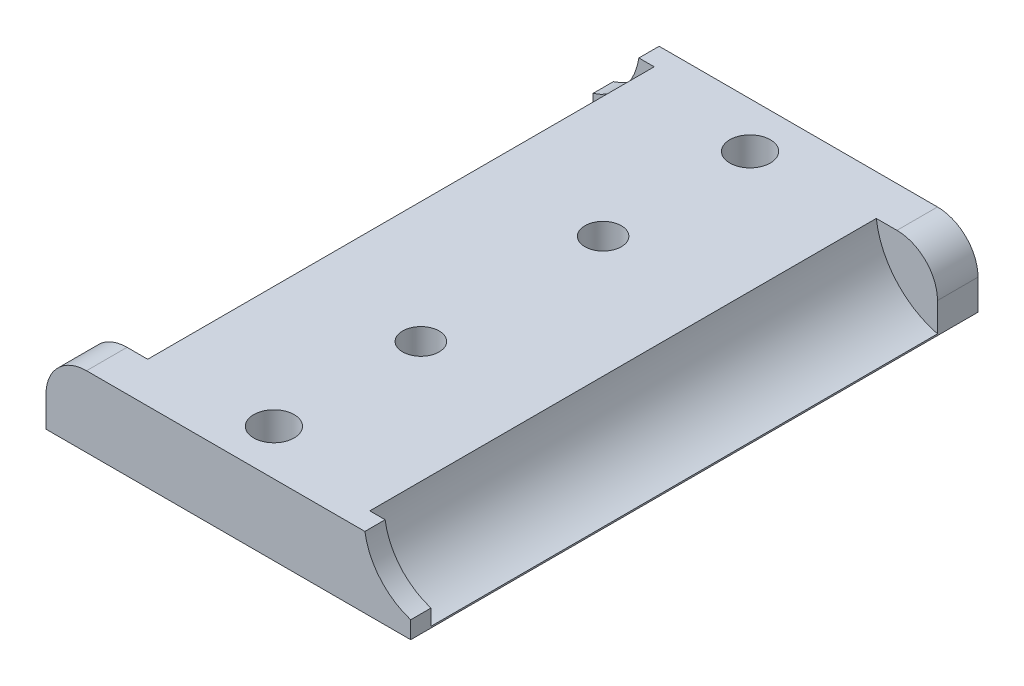
SolidWorks part; units mm, degrees
ref_plane "Front Plane" through (0, 0, 0) normal (0, 0, 1) x (1, 0, 0)
ref_plane "Top Plane" through (0, 0, 0) normal (0, 1, 0) x (1, 0, 0)
ref_plane "Right Plane" through (0, 0, 0) normal (1, 0, 0) x (0, 0, -1)
sketch "Sketch1" plane through (0, 0, 0) normal (0, 1, 0) x (1, 0, 0)
  line L1 (13.1473, -19.7747) -> (-4.8527, -19.7747)
  line L2 (13.1473, -19.7747) -> (13.1473, -47.7747)
  line L3 (13.1473, -47.7747) -> (-4.8527, -47.7747)
  line L4 (-4.8527, -19.7747) -> (-4.8527, -47.7747)
  dimension "D1" = 18
  dimension "D2" = 28
extrude "Boss-Extrude1" add sketch "Sketch1" along normal blind 4
sketch "Sketch2" plane through (0, 0, 19.7747) normal (0, 0, -1) x (-1, 0, 0)
  circle A0 centre (-14.1473, 4) radius 4.05
  circle A1 centre (5.8527, 4) radius 4.05
  dimension "D1" = 8.1
  dimension "D2" = 8.1
extrude "Cut-Extrude1" cut sketch "Sketch2" against normal through all
sketch "Sketch3" plane through (0, 4, 0) normal (0, 1, 0) x (1, 0, 0)
  circle A0 centre (4.1473, -38.2722) radius 0.9
  circle A1 centre (4.1473, -29.2771) radius 0.9
  dimension "D1" = 1.8
  dimension "D2" = 1.8
extrude "Cut-Extrude2" cut sketch "Sketch3" against normal blind 5
sketch "Sketch4" plane through (0, 0, 0) normal (0, -1, 0) x (1, 0, 0)
  circle A0 centre (4.1473, 29.2771) radius 1.6
  circle A1 centre (4.1473, 38.2722) radius 1.6
  dimension "D1" = 3.2
  dimension "D2" = 3.2
extrude "Cut-Extrude3" cut sketch "Sketch4" against normal blind 2
sketch "Sketch5" plane through (0, 4, 0) normal (0, 1, 0) x (1, 0, 0)
  line L0 (13.1473, -19.7747) -> (13.1473, -47.7747) construction
  line L1 (10.0973, -19.7747) -> (13.1473, -19.7747)
  line L2 (10.0973, -19.7747) -> (10.0973, -21.7747)
  line L3 (10.0973, -21.7747) -> (13.1473, -21.7747)
  line L4 (13.1473, -19.7747) -> (13.1473, -21.7747)
  line L5 (-4.8527, -47.7747) -> (-4.8527, -19.7747) construction
  line L6 (-1.8027, -47.7747) -> (-4.8527, -47.7747)
  line L7 (-1.8027, -47.7747) -> (-1.8027, -45.7747)
  line L8 (-1.8027, -45.7747) -> (-4.8527, -45.7747)
  line L9 (-4.8527, -47.7747) -> (-4.8527, -45.7747)
  dimension "D1" = 2
  dimension "D2" = 2
extrude "Boss-Extrude2" add sketch "Sketch5" against normal up to surface (4 mm away) up to face at (4.1473, 0, 27.6771)
sketch "Sketch6" plane through (0, 4, 0) normal (0, 1, 0) x (1, 0, 0)
  line L0 (13.1473, -21.7747) -> (13.1473, -47.7747) construction
  line L1 (10.0973, -47.7747) -> (13.1473, -47.7747)
  line L2 (10.0973, -47.7747) -> (10.0973, -46.7747)
  line L3 (10.0973, -46.7747) -> (13.1473, -46.7747)
  line L4 (13.1473, -47.7747) -> (13.1473, -46.7747)
  line L5 (-4.8527, -45.7747) -> (-4.8527, -19.7747) construction
  line L6 (-1.8027, -19.7747) -> (-4.8527, -19.7747)
  line L7 (-1.8027, -19.7747) -> (-1.8027, -20.7747)
  line L8 (-1.8027, -20.7747) -> (-4.8527, -20.7747)
  line L9 (-4.8527, -19.7747) -> (-4.8527, -20.7747)
  dimension "D1" = 1
  dimension "D2" = 1
extrude "Boss-Extrude3" add sketch "Sketch6" against normal up to surface (4 mm away) up to face at (4.1473, 0, 33.7747)
sketch "Sketch7" plane through (0, 0, 47.7747) normal (0, 0, 1) x (1, 0, 0)
  circle A0 centre (14.1473, 4) radius 3.3
  dimension "D1" = 6.6
extrude "Cut-Extrude4" cut sketch "Sketch7" against normal blind 2
sketch "Sketch8" plane through (0, 0, 19.7747) normal (0, 0, -1) x (-1, 0, 0)
  circle A0 centre (5.8527, 4) radius 3.3
  dimension "D1" = 6.6
extrude "Cut-Extrude5" cut sketch "Sketch8" against normal blind 2
sketch "Sketch9" plane through (0, 4, 0) normal (0, 1, 0) x (1, 0, 0)
  circle A0 centre (4.1473, -45.5247) radius 1
  circle A1 centre (4.1473, -22.0247) radius 1
  dimension "D1" = 2
  dimension "D2" = 2
extrude "Cut-Extrude6" cut sketch "Sketch9" against normal through all
sketch "Sketch10" plane through (0, 0, 0) normal (0, -1, 0) x (1, 0, 0)
  circle A0 centre (4.1473, 45.5247) radius 1.6
  circle A1 centre (4.1473, 22.0247) radius 1.6
  dimension "D1" = 3.2
  dimension "D2" = 3.2
extrude "Cut-Extrude7" cut sketch "Sketch10" against normal blind 1.5
sketch "Sketch11" plane through (0, 0, 19.7747) normal (0, 0, -1) x (-1, 0, 0)
  line L0 (4.8527, 0.0754) -> (4.8527, 4) construction
  line L1 (-13.1473, 4) -> (4.8527, 4)
  line L2 (-13.1473, 4) -> (-13.1473, 3.5)
  line L3 (-13.1473, 3.5) -> (4.8527, 3.5)
  line L4 (4.8527, 4) -> (4.8527, 3.5)
  dimension "D1" = 0.5
extrude "Cut-Extrude8" cut sketch "Sketch11" against normal through all
fillet "Fillet2" radius 2 2 edges at (-4.8527, 3.5, 46.7747) (13.1473, 3.5, 20.7747)
